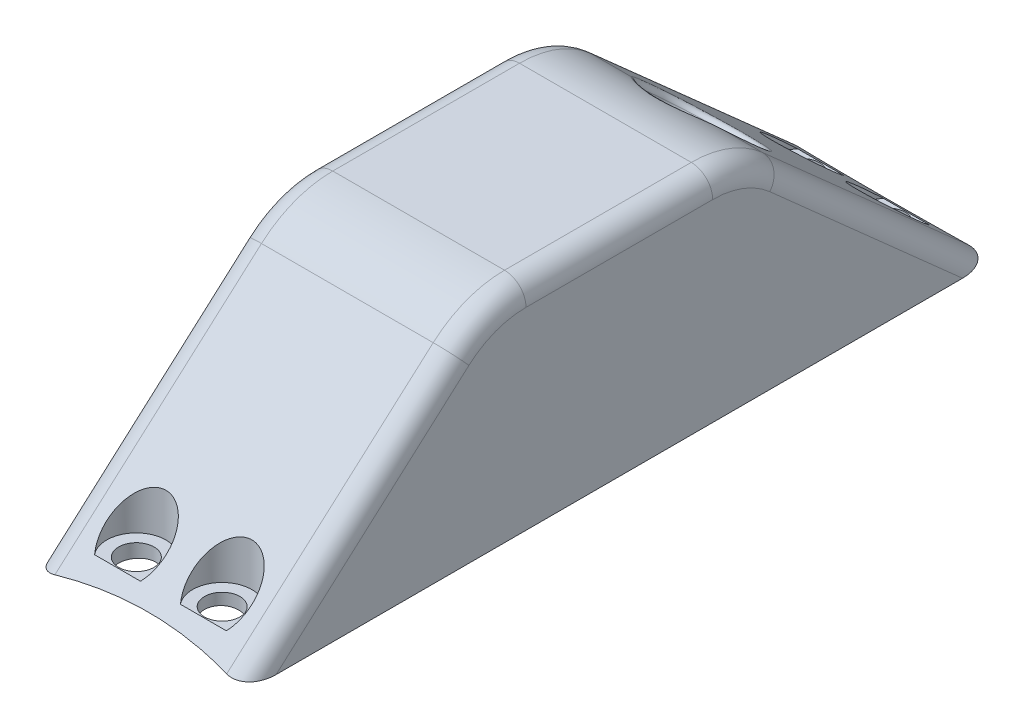
SolidWorks part; units mm, degrees
ref_plane "Front Plane" through (0, 0, 0) normal (0, 0, 1) x (1, 0, 0)
ref_plane "Top Plane" through (0, 0, 0) normal (0, 1, 0) x (1, 0, 0)
ref_plane "Right Plane" through (0, 0, 0) normal (1, 0, 0) x (0, 0, -1)
sketch "Sketch1" plane through (0, 0, 0) normal (0, 1, 0) x (1, 0, 0)
  line L0 (-14.05, 27.5) -> (14.05, 27.5)
  line L1 (-14.05, 27.5) -> (-14.05, -27.5)
  line L2 (14.05, 27.5) -> (14.05, -27.5)
  line L3 (-14.05, -27.5) -> (14.05, -27.5)
  line L4 (-14.05, 27.5) -> (14.05, -27.5) construction
  line L5 (14.05, 27.5) -> (-14.05, -27.5) construction
  point P1 (0, 0)
  dimension "D1" = 28.1
  dimension "D2" = 55
ref_plane "Plane1" through (0, 20, 0) normal (0, 1, 0) x (1, 0, 0)
sketch "Sketch2" plane through (0, 0, 0) normal (1, 0, 0) x (0, 0, -1)
  line L0 (-35, 0) -> (35, 0)
  line L1 (0, 0) -> (0, 20) construction
  line L2 (15.455, 20) -> (-15.455, 20) construction
  line L3 (-8.698, 20) -> (8.698, 20)
  line L4 (-35, 0) -> (-15.3416, 17.4741)
  line L5 (15.3416, 17.4741) -> (35, 0)
  arc A0 (8.698, 20) -> (15.3416, 17.4741) centre (8.698, 10) cw
  arc A1 (-8.698, 20) -> (-15.3416, 17.4741) centre (-8.698, 10) ccw
  point P4 (0, 0)
  point P12 (0, 20)
  point P14 (12.5, 20)
  point P17 (-12.5, 20)
  dimension "D3" = 10
  dimension "D1" = 70
  dimension "D2" = 25
extrude "Boss-Extrude1" add sketch "Sketch2" along normal blind 20
fillet "Fillet1" radius 2 10 edges at (20, 8.737, -25.1708) (20, 19.3472, -12.2518) (20, 8.737, 25.1708) (20, 19.3472, 12.2518) (20, 20, 0) (0, 8.737, -25.1708) (0, 19.3472, -12.2518) (0, 20, 0) (0, 19.3472, 12.2518) (0, 8.737, 25.1708)
ref_plane "Plane2" through (0, -17.3793, -19.5517) normal (0, -0.6644, -0.7474) x (-1, 0, 0)
sketch "Sketch3" plane through (0, -17.3793, -19.5517) normal (0, -0.6644, -0.7474) x (-1, 0, 0)
  line L0 (-18, 23.2527) -> (-2, 23.2527) construction
  line L1 (-17.05, 10.2527) -> (-2.95, 10.2527)
  line L2 (-17.05, 10.2527) -> (-17.05, -9.2473)
  line L3 (-17.05, -9.2473) -> (-2.95, -9.2473)
  line L4 (-2.95, 10.2527) -> (-2.95, -9.2473)
  line L5 (-20, -21.2527) -> (-20, 21.2527) construction
  line L7 (0, -21.2527) -> (0, 21.2527) construction
  dimension "D1" = 2.95
  dimension "D2" = 19.5
  dimension "D3" = 13
  dimension "D4" = 2.95
extrude "Cut-Extrude1" cut sketch "Sketch3" against normal blind 34 contours L2 L1 L4 L3
sketch "Sketch4" plane through (0, 7.663, -6.8115) normal (0, -0.7474, 0.6644) x (1, 0, 0)
  line L0 (2.95, 7.8407) -> (2.95, -11.5343) construction
  line L1 (2.95, 5.6657) -> (17.05, 5.6657)
  line L2 (2.95, 5.6657) -> (2.95, -11.5343)
  line L3 (2.95, -11.5343) -> (17.05, -11.5343)
  line L4 (17.05, 5.6657) -> (17.05, -11.5343)
  line L5 (17.05, 7.8407) -> (17.05, -11.5343) construction
  line L7 (10, 5.6657) -> (10, -11.5343) construction
  line L8 (2.95, -2.9343) -> (17.05, -2.9343) construction
  line L9 (2.95, -11.5343) -> (17.05, -11.5343) construction
  line L10 (2.95, -9.4343) -> (17.05, -9.4343)
  line L11 (2.95, -9.4343) -> (2.95, 3.5657)
  line L12 (2.95, 3.5657) -> (17.05, 3.5657)
  line L13 (17.05, -9.4343) -> (17.05, 3.5657)
  line L14 (2.95, -9.4343) -> (17.05, 3.5657) construction
  line L15 (2.95, 3.5657) -> (17.05, -9.4343) construction
  line L16 (4.05, -8.8343) -> (15.95, -8.8343)
  line L17 (4.05, -8.8343) -> (4.05, 2.9657)
  line L18 (4.05, 2.9657) -> (15.95, 2.9657)
  line L19 (15.95, -8.8343) -> (15.95, 2.9657)
  line L20 (4.05, -8.8343) -> (15.95, 2.9657) construction
  line L21 (4.05, 2.9657) -> (15.95, -8.8343) construction
  circle A0 centre (10, -2.9343) radius 4.75
  point P14 (10, -2.9343)
  point P19 (10, -2.9343)
  dimension "D6" = 9.5
  dimension "D1" = 17.2
  dimension "D3" = 13
  dimension "D4" = 11.8
  dimension "D5" = 11.9
extrude "Cut-Extrude2" cut sketch "Sketch4" against normal blind 20 contours A0 | A0 region at (10, 5.7135, -9.0047)
extrude "Cut-Extrude3" cut sketch "Sketch4<5>" against normal blind 11 contours L16 L19 L18 L17 A0 region at (4.2176, 5.7135, -9.0047)
sketch "Sketch4<5>" plane through (0, 7.663, -6.8115) normal (0, -0.7474, 0.6644) x (1, 0, 0) same geometry as "Sketch4"
extrude "Cut-Extrude4" cut sketch "Sketch4<6>" against normal blind 5.6 contours L12 L2 L10 L4 L19 L16 L17 L18 region at (10, 9.9045, -4.2899)
sketch "Sketch4<6>" plane through (0, 7.663, -6.8115) normal (0, -0.7474, 0.6644) x (1, 0, 0) same geometry as "Sketch4"
extrude "Cut-Extrude5" cut sketch "Sketch4<8>" against normal blind 2.4 contours L1 L4 L3 L2
sketch "Sketch4<8>" plane through (0, 7.663, -6.8115) normal (0, -0.7474, 0.6644) x (1, 0, 0) same geometry as "Sketch4"
fillet "Fillet2" radius 0.5 2 edges at (10, 12.2741, -21.1916) (9.3266, 18.4544, -14.0388)
ref_plane "Plane3" through (0, 10, 0) normal (0, 1, 0) x (1, 0, 0)
sketch "Sketch7" plane through (0, 10, 0) normal (0, 1, 0) x (1, 0, 0)
  line L0 (18, 35) -> (2, 35) construction
  line L1 (18, 15.3416) -> (18, 35) construction
  line L2 (10, 35) -> (10, -35) construction
  line L3 (18, -35) -> (2, -35) construction
  line L4 (10, 0) -> (20, 0) construction
  line L5 (20, 8.698) -> (20, -8.698) construction
  circle A0 centre (14, 31) radius 1.65
  circle A1 centre (6, 31) radius 1.65
  circle A2 centre (14, -31) radius 1.65
  circle A3 centre (6, -31) radius 1.65
  circle A4 centre (14, 31) radius 2.765
  circle A5 centre (6, 31) radius 2.765
  circle A6 centre (6, -31) radius 2.765
  circle A7 centre (14, -31) radius 2.765
  dimension "D1" = 3.3
  dimension "D2" = 4
  dimension "D3" = 4
  dimension "D4" = 5.53
  dimension "D5" = 2
  dimension "D6" = 2
extrude "Cut-Extrude7" cut sketch "Sketch7" against normal blind 15 contours A3 | A2 | A1 | A0 region at (14, 10, -31) region at (6, 10, -31) region at (14, 10, 31) region at (6, 10, 31)
extrude "Cut-Extrude8" cut sketch "Sketch7<3>" against normal blind 8 contours A4 A0 | A6 A3 | A7 A2 | A5 region at (11.3132, 10, -31) region at (3.3132, 10, 31) region at (11.3132, 10, 31)
sketch "Sketch7<3>" plane through (0, 10, 0) normal (0, 1, 0) x (1, 0, 0) same geometry as "Sketch7"
sketch "Sketch8" plane through (0, 0, 0) normal (0, 0, 1) x (1, 0, 0)
  line L0 (10.0058, 19.9927) -> (10.0058, -24.1728) construction
  line L1 (10.0058, -24.1728) -> (10.0058, -52.5968) construction
  line L2 (20, 0) -> (10.0058, -50)
  line L3 (0, 0) -> (20, 0)
  circle A0 centre (10.0058, -50) radius 51
  dimension "D1" = 50
extrude "Cut-Extrude9" cut sketch "Sketch8" against normal blind 49 and the other way blind 41 contours A0 region at (-39.5517, -50, 0)
